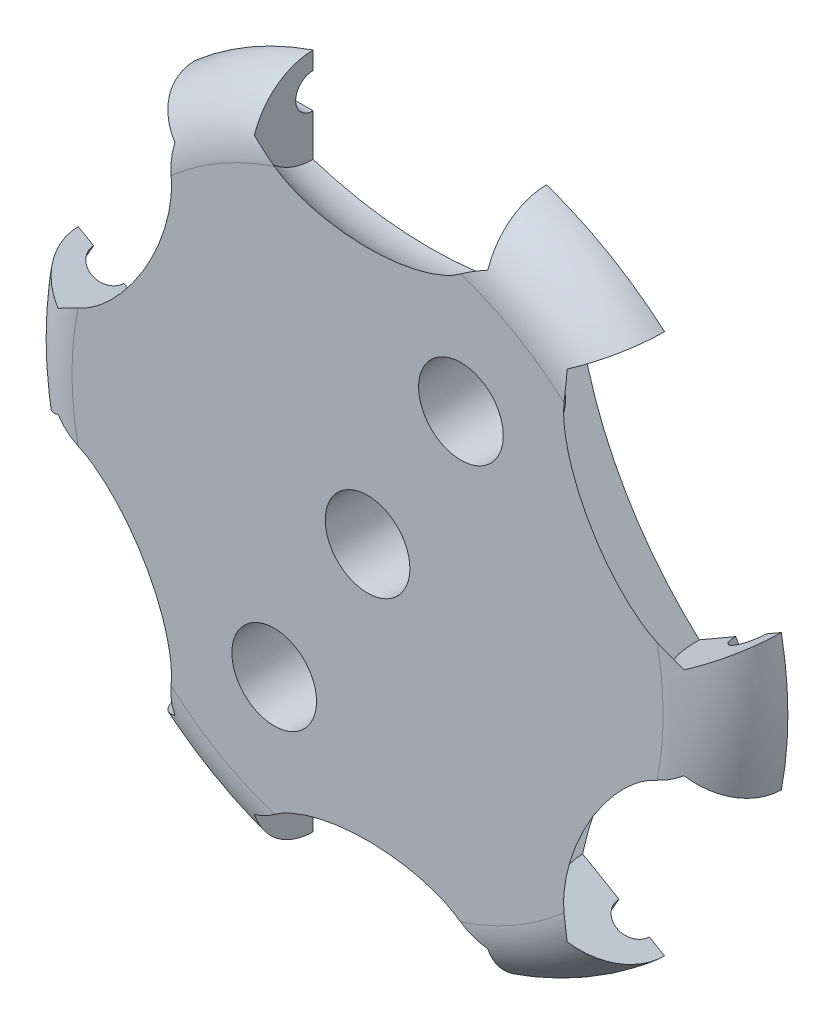
SolidWorks part; units mm, degrees
ref_plane "Front Plane" through (0, 0, 0) normal (0, 0, 1) x (1, 0, 0)
ref_plane "Top Plane" through (0, 0, 0) normal (0, 1, 0) x (1, 0, 0)
ref_plane "Right Plane" through (0, 0, 0) normal (1, 0, 0) x (0, 0, -1)
sketch "Sketch1" plane through (0, 0, 0) normal (0, 0, 1) x (1, 0, 0)
  circle A0 centre (0, 0) radius 18.2626
  dimension "D1" = 36.5252
extrude "Boss-Extrude1" add sketch "Sketch1" along normal blind 3.175
fillet "Fillet1" radius 3.1852 1 edges at (18.2626, 0, 3.175)
sketch "Sketch2" plane through (0, 0, 3.175) normal (0, 0, 1) x (1, 0, 0)
  line L0 (-4.7625, -8.2489) -> (4.7625, 8.2489) construction
  line L1 (0, 0) -> (0, 6.4682) construction
  circle A0 centre (4.7625, 8.2489) radius 2.159
  circle A1 centre (-4.7625, -8.2489) radius 2.159
  circle A4 centre (0, 0) radius 2.159
  point P9 (0, 0)
  dimension "D2" = 4.318
  dimension "D4" = 4.318
  dimension "D1" = 9.525
  dimension "D5" = 30
  dimension "D3" = 2
extrude "Cut-Extrude1" cut sketch "Sketch2" against normal through all
sketch "Sketch5" plane through (0, 0, 0) normal (0, 0, 1) x (1, 0, 0)
  line L0 (-5.9531, 15.4686) -> (5.9531, 15.4686)
  line L1 (5.9531, 15.4686) -> (5.9531, 18.5033)
  line L2 (-5.9531, 15.4686) -> (-5.9531, 18.5033)
  line L3 (-5.9531, 15.4686) -> (-8.5086, 15.4686) construction
  arc A0 (-5.9531, 18.5033) -> (5.9531, 18.5033) centre (0, 0) cw
  circle A1 centre (0, 0) radius 18.2626 construction
  point P5 (0, 15.4686)
  point P9 (0, 19.4373)
  dimension "D1" = 11.9062
  dimension "D2" = 15.4686
  dimension "D3" = 7.9375
revolve "Cut-Revolve1" cut sketch "Sketch5" angle 360 about L3
sketch "Sketch6" plane through (0, 0, 0) normal (1, 0, 0) x (0, 0, -1)
  line L0 (0, -18.2626) -> (0, 17.2651) construction
  circle A0 centre (0, 15.4686) radius 0.889
  arc A1 (-2.9966, 14.9895) -> (0, 12.4339) centre (0, 15.4686) ccw construction
  dimension "D1" = 1.778
extrude "Cut-Extrude2" cut sketch "Sketch6" against normal mid plane 15.875
pattern_circular "CirPattern1" count 6 over 360 about axis through (0, 0, 0) along (0, 0, 1) of "Cut-Revolve1", "Cut-Extrude2"
sketch "Sketch8" plane through (0, 0, 3.175) normal (0, 0, 1) x (1, 0, 0)
  line L1 (0, 5.1326) -> (-4.445, 2.5663)
  line L2 (-4.445, 2.5663) -> (-4.445, -2.5663)
  line L3 (-4.445, -2.5663) -> (0, -5.1326)
  line L4 (0, -5.1326) -> (4.445, -2.5663)
  line L5 (4.445, -2.5663) -> (4.445, 2.5663)
  line L6 (4.445, 2.5663) -> (0, 5.1326)
  circle A0 centre (0, 0) radius 4.445 construction
  dimension "D1" = 8.89
extrude "Cut-Extrude4" [suppressed] cut sketch "Sketch8" against normal blind 1.5875
